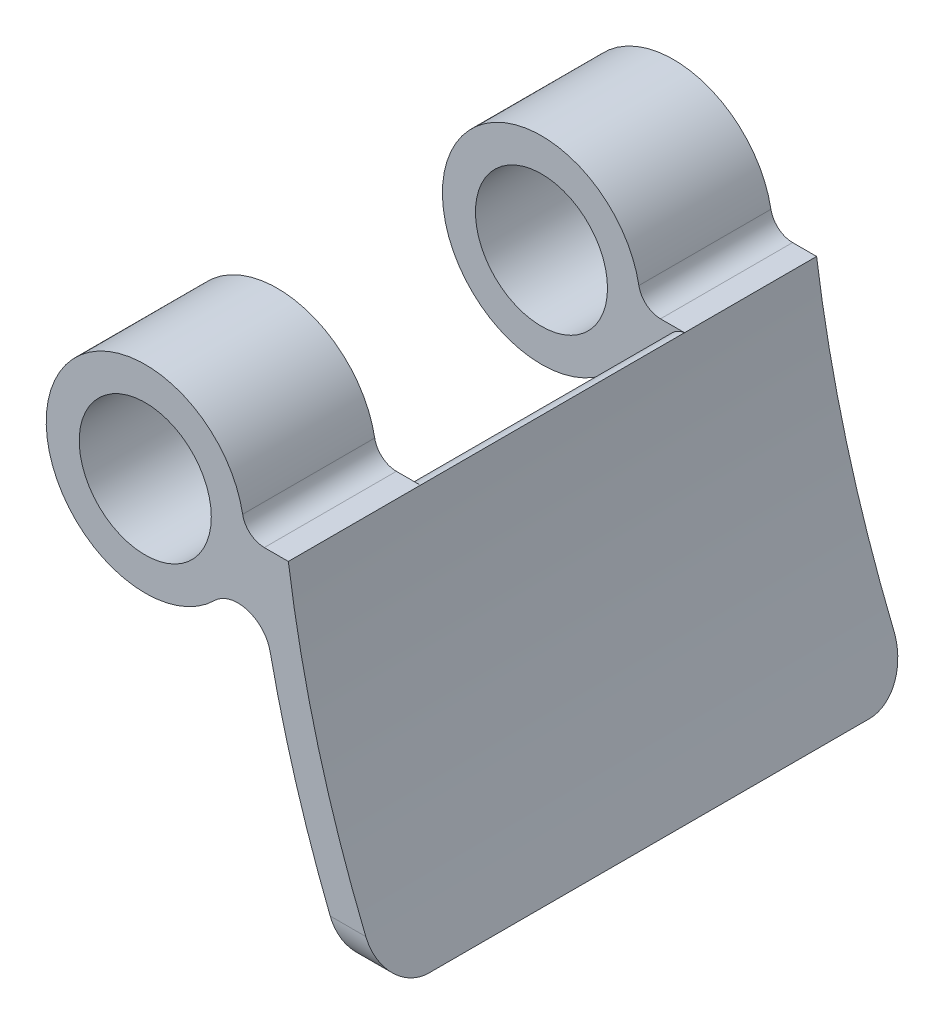
SolidWorks part; units mm, degrees
material "No.2 BRASS"
ref_plane "Front Plane" through (0, 0, 0) normal (0, 0, 1) x (1, 0, 0)
ref_plane "Top Plane" through (0, 0, 0) normal (0, 1, 0) x (1, 0, 0)
ref_plane "Right Plane" through (0, 0, 0) normal (1, 0, 0) x (0, 0, -1)
sketch "Sketch1" plane through (0, 0, 0) normal (0, 0, 1) x (1, 0, 0)
  line L0 (14.2875, 0) -> (20.6375, 0)
  line L1 (26.8703, 0) -> (-26.8703, 0) construction
  line L2 (34.5676, -47.625) -> (29.3434, -47.625)
  line L3 (12.6479, -47.625) -> (9.802, -47.625)
  line L4 (14.2875, -4.7625) -> (16.5456, -4.7625) construction
  arc A0 (14.2875, 0) -> (10.0174, -10.1874) centre (0, 0) ccw
  arc A1 (20.6375, 0) -> (34.5676, -47.625) centre (190.4258, 23.8125) ccw
  arc A2 (18.0163, -12.5991) -> (29.3434, -47.625) centre (190.4258, 23.8125) ccw
  arc A3 (10.0174, -10.1874) -> (18.0163, -12.5991) centre (13.3566, -13.5832) cw
  arc A6 (16.5456, -4.7625) -> (30.2382, -49.6094) centre (190.4258, 23.8125) ccw construction
  dimension "D1" = 28.575
  dimension "D2" = 171.45
  dimension "D4" = 4.7625
  dimension "D5" = 4.7625
  dimension "D7" = 23.8125
  dimension "D8" = 47.625
  dimension "D3" = 20.6375
extrude "Boss-Extrude1" add sketch "Sketch1" along normal mid plane 76.2 contours A0 A3 A2 L2 A1 L0
fillet "Fillet1" radius 3.175 1 edges at (14.2875, 0, 0)
fillet "Fillet2" radius 6.35 1 edges at (31.9555, -47.625, 38.1)
fillet "Fillet3" radius 6.35 1 edges at (31.9555, -47.625, -38.1)
fillet "Fillet4" radius 3.175 1 edges at (29.3434, -47.625, 0) tangent propagation no
sketch "Sketch4" plane through (0, 0, 38.1) normal (0, 0, 1) x (1, 0, 0)
  line L2 (26.6746, -41.275) -> (31.8108, -41.275)
  line L3 (20.6375, 0) -> (17.1714, 0)
  line L4 (26.6746, -41.275) -> (31.8108, -41.275)
  line L5 (20.6375, 0) -> (17.1714, 0)
  circle A0 centre (0, 0) radius 9.525
  arc A5 (18.0163, -12.5991) -> (26.6746, -41.275) centre (190.4258, 23.8125) ccw
  arc A6 (20.6375, 0) -> (31.8108, -41.275) centre (190.4258, 23.8125) ccw
  arc A7 (14.0494, 2.5977) -> (17.1714, 0) centre (17.1714, 3.175) ccw
  arc A8 (14.0494, 2.5977) -> (10.0174, -10.1874) centre (0, 0) ccw
  arc A9 (18.0163, -12.5991) -> (10.0174, -10.1874) centre (13.3566, -13.5832) ccw
  arc A10 (18.0163, -12.5991) -> (26.6746, -41.275) centre (190.4258, 23.8125) ccw
  arc A11 (20.6375, 0) -> (31.8108, -41.275) centre (190.4258, 23.8125) ccw
  arc A12 (14.0494, 2.5977) -> (17.1714, 0) centre (17.1714, 3.175) ccw
  arc A13 (14.0494, 2.5977) -> (10.0174, -10.1874) centre (0, 0) ccw
  arc A14 (18.0163, -12.5991) -> (10.0174, -10.1874) centre (13.3566, -13.5832) ccw
  dimension "D2" = 19.05
  dimension "D1" = 0
extrude "Cut-Extrude2" cut sketch "Sketch4" against normal through all and the other way through all contours A0
sketch "Sketch6" plane through (0, 0, 0) normal (0, 0, 1) x (1, 0, 0)
  line L0 (12.6479, -47.625) -> (9.802, -47.625) construction
  line L1 (12.6479, -47.625) -> (9.802, -47.625)
  line L2 (29.3434, -47.625) -> (34.5676, -47.625)
  line L3 (20.6375, 0) -> (14.2875, 0)
  line L4 (29.3434, -47.625) -> (31.0816, -47.625)
  line L5 (20.6375, 0) -> (17.1714, 0)
  line L6 (20.6375, 0) -> (17.4933, -0.441)
  arc A0 (17.4933, -0.441) -> (31.0816, -47.625) centre (190.4258, 23.8125) ccw
  arc A1 (14.0494, 2.5977) -> (17.1714, 0) centre (17.1714, 3.175) ccw
  arc A4 (20.6375, 0) -> (34.5676, -47.625) centre (190.4258, 23.8125) ccw
  arc A5 (14.2875, 0) -> (10.0174, -10.1874) centre (0, 0) ccw
  arc A6 (18.0163, -12.5991) -> (10.0174, -10.1874) centre (13.3566, -13.5832) ccw
  arc A7 (18.0163, -12.5991) -> (29.3434, -47.625) centre (190.4258, 23.8125) ccw
  arc A9 (14.0494, 2.5977) -> (10.0174, -10.1874) centre (0, 0) ccw
  arc A10 (18.0163, -12.5991) -> (10.0174, -10.1874) centre (13.3566, -13.5832) ccw
  arc A11 (18.0163, -12.5991) -> (29.3434, -47.625) centre (190.4258, 23.8125) ccw
  dimension "D2" = 3.175
  dimension "D1" = 0
extrude "Cut-Extrude4" cut sketch "Sketch6" against normal mid plane 38.1 contours A9 A10 A11 L4 A0 L6 L5 A1
fillet "Fillet5" radius 3.175 1 edges at (17.4933, -0.441, 0)
